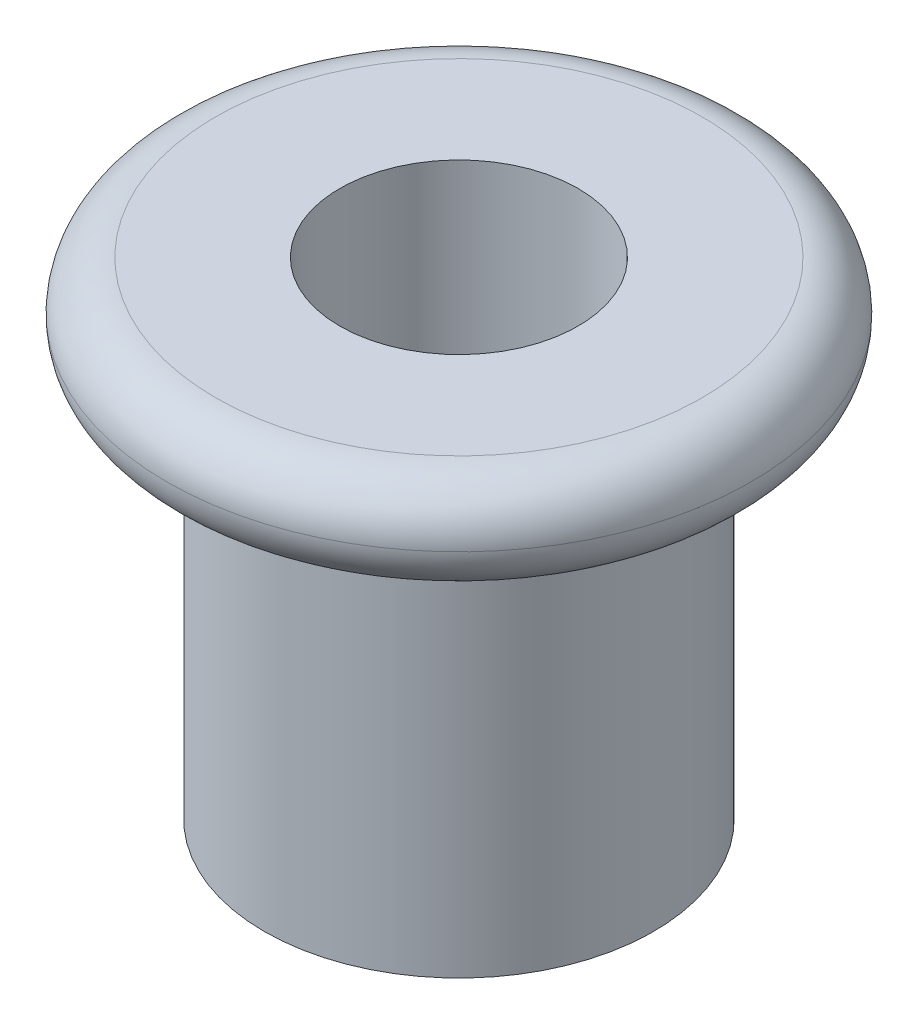
SolidWorks part; units mm, degrees
ref_plane "Front" through (0, 0, 0) normal (0, 0, 1) x (1, 0, 0)
ref_plane "Top" through (0, 0, 0) normal (0, 1, 0) x (1, 0, 0)
ref_plane "Right" through (0, 0, 0) normal (1, 0, 0) x (0, 0, -1)
sketch "Sketch1" plane through (0, 0, 0) normal (0, 1, 0) x (1, 0, 0)
  circle A0 centre (0, 0) radius 2.45
  circle A1 centre (0, 0) radius 4
  dimension "D1" = 4.9
  dimension "D2" = 8
extrude "Boss-Extrude1" add sketch "Sketch1" along normal blind 8
sketch "Sketch2" plane through (0, 8, 0) normal (0, 1, 0) x (1, 0, 0)
  circle A0 centre (0, 0) radius 6
  dimension "D1" = 12
extrude "Boss-Extrude2" add sketch "Sketch2" along normal blind 2
fillet "Fillet1" radius 1 2 edges at (0, 10, 6) (0, 8, 6)
sketch "Sketch3" plane through (0, 10, 0) normal (0, 1, 0) x (1, 0, 0)
  circle A0 centre (0, 0) radius 2.45
  dimension "D1" = 4.9
extrude "Cut-Extrude1" cut sketch "Sketch3" against normal up to next
chamfer "Chamfer1" distance 1 angle 45 1 edges at (0, 0, 2.45)
